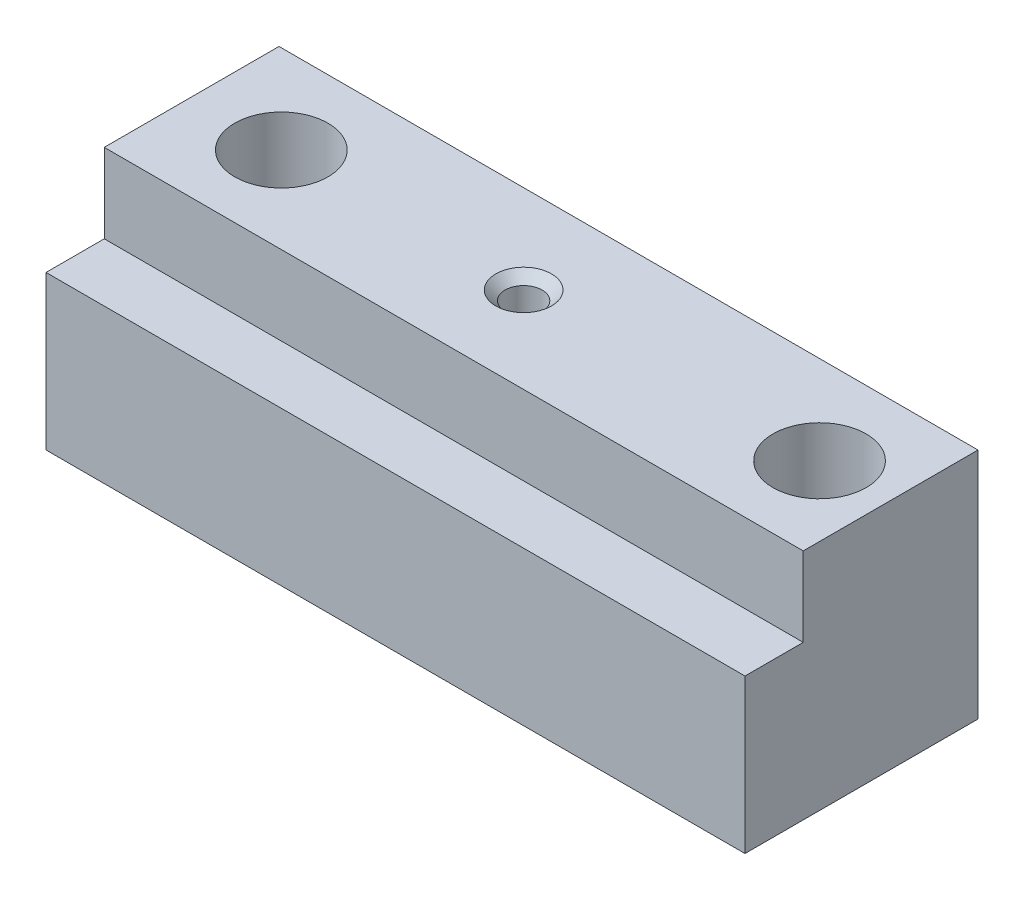
SolidWorks part; units mm, degrees
ref_plane "Front Plane" through (0, 0, 0) normal (0, 0, 1) x (1, 0, 0)
ref_plane "Top Plane" through (0, 0, 0) normal (0, 1, 0) x (1, 0, 0)
ref_plane "Right Plane" through (0, 0, 0) normal (1, 0, 0) x (0, 0, -1)
sketch "Sketch1" plane through (0, 0, 0) normal (1, 0, 0) x (0, 0, -1)
  line L0 (0, 0) -> (-6.35, 0)
  line L1 (-6.35, 0) -> (-6.35, -16.764)
  line L2 (-6.35, -16.764) -> (19.05, -16.764)
  line L3 (19.05, -16.764) -> (19.05, 8.636)
  line L4 (19.05, 8.636) -> (0, 8.636)
  line L5 (0, 8.636) -> (0, 0)
  dimension "D1" = 25.4
  dimension "D2" = 25.4
  dimension "D3" = 8.636
  dimension "D4" = 6.35
extrude "Boss-Extrude1" add sketch "Sketch1" along normal blind 38.1 and the other way blind 38.1
sketch "Sketch2" plane through (0, 8.636, 0) normal (0, 1, 0) x (1, 0, 0)
  line L0 (-38.1, 19.05) -> (-38.1, 9.398) construction
  line L1 (-38.1, 19.05) -> (-38.1, 0) construction
  line L2 (-38.1, 9.398) -> (-28.194, 9.398) construction
  line L3 (-28.194, 9.398) -> (-1.778, 9.398) construction
  line L4 (-1.778, 9.398) -> (30.48, 9.398) construction
  line L5 (30.48, 9.398) -> (38.1, 9.398) construction
  line L6 (38.1, 19.05) -> (38.1, 0) construction
  circle A0 centre (-28.194, 9.398) radius 5.08
  circle A2 centre (30.48, 9.398) radius 5.08
  point P14 (0, 0)
  dimension "D5" = 10.16
  dimension "D6" = 10.16
  dimension "D1" = 9.652
  dimension "D2" = 26.416
  dimension "D3" = 32.258
  dimension "D4" = 7.62
extrude "Cut-Extrude1" cut sketch "Sketch2" against normal blind 19.05
sketch "Sketch6" plane through (0, 8.636, 0) normal (0, 1, 0) x (1, 0, 0)
  line L0 (-28.194, 9.398) -> (-1.778, 9.398) construction
  line L1 (-1.778, 9.398) -> (-1.778, 19.05) construction
  line L3 (-38.1, 19.05) -> (38.1, 19.05) construction
  dimension "D1" = 26.416
hole_wizard "#10-32 Tapped Hole2" positions "3DSketch1" profile "Sketch7" tap size "#10-32" standard "ANSI Inch" end condition through all
sketch3d "3DSketch1"
  point P0 (-1.778, 8.636, -9.398)
sketch "Sketch7" plane through (-1.778, 8.636, -9.398) normal (1, 0, 0) x (0, 0, 1)
  line L0 (0, 0) -> (0, 25.4)
  line L1 (0, 25.4) -> (2.0193, 25.4)
  line L2 (2.0193, 25.4) -> (2.0193, 0)
  line L5 (2.0193, 0) -> (0, 0)
  line L11 (0, -6.35) -> (0, 107.95) construction
  dimension "Thru Tap Drill Dia." = 4.0386
  dimension "Thru Tap Drill Depth" = 25.4
cosmetic thread "Hole Thread2"
chamfer "Chamfer5" distance 1.016 angle 45 1 edges at (-1.778, 8.636, -7.3787)
chamfer "Chamfer6" distance 1.016 angle 45 1 edges at (-1.778, -16.764, -7.3787)
